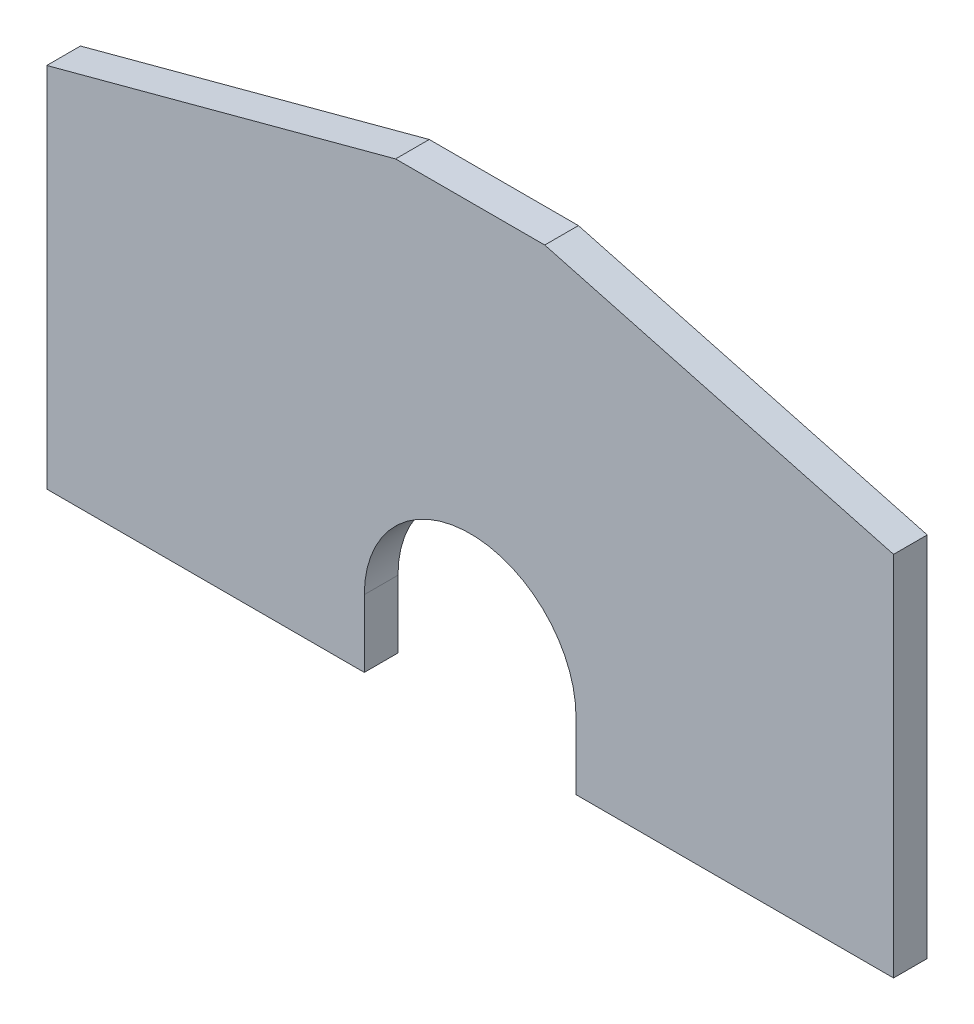
SolidWorks part; units mm, degrees
material "Titan Ti-8Mn, Gehärtet"
ref_plane "Ebene vorne" through (0, 0, 0) normal (0, 0, 1) x (1, 0, 0)
ref_plane "Ebene oben" through (0, 0, 0) normal (0, 1, 0) x (1, 0, 0)
ref_plane "Ebene rechts" through (0, 0, 0) normal (1, 0, 0) x (0, 0, -1)
sketch "Skizze1" plane through (0, 0, 0) normal (0, 0, 1) x (1, 0, 0)
  line L1 (62.8775, 389.0766) -> (62.8775, 7.8066)
  line L2 (62.8775, 7.8066) -> (-267.1225, 7.8066)
  line L3 (-267.1225, 7.8066) -> (-267.1225, 77.8066)
  line L4 (-817.1225, 389.0766) -> (-817.1225, 7.8066)
  line L5 (-817.1225, 7.8066) -> (-487.1225, 7.8066)
  line L6 (-487.1225, 7.8066) -> (-487.1225, 77.8066)
  line L7 (-817.1225, 389.0766) -> (-454.6225, 486.2082)
  line L8 (-454.6225, 486.2082) -> (-299.6225, 486.2082)
  line L9 (-299.6225, 486.2082) -> (62.8775, 389.0766)
  arc A0 (-487.1225, 77.8066) -> (-267.1225, 77.8066) centre (-377.1225, 77.8066) cw
  dimension "D1" = 330
  dimension "D2" = 155
  dimension "D3" = 70
  dimension "D4" = 381.27
  dimension "D5" = 105
  dimension "D6" = 880
extrude "Aufsatz-Linear austragen1" add sketch "Skizze1" along normal blind 35
